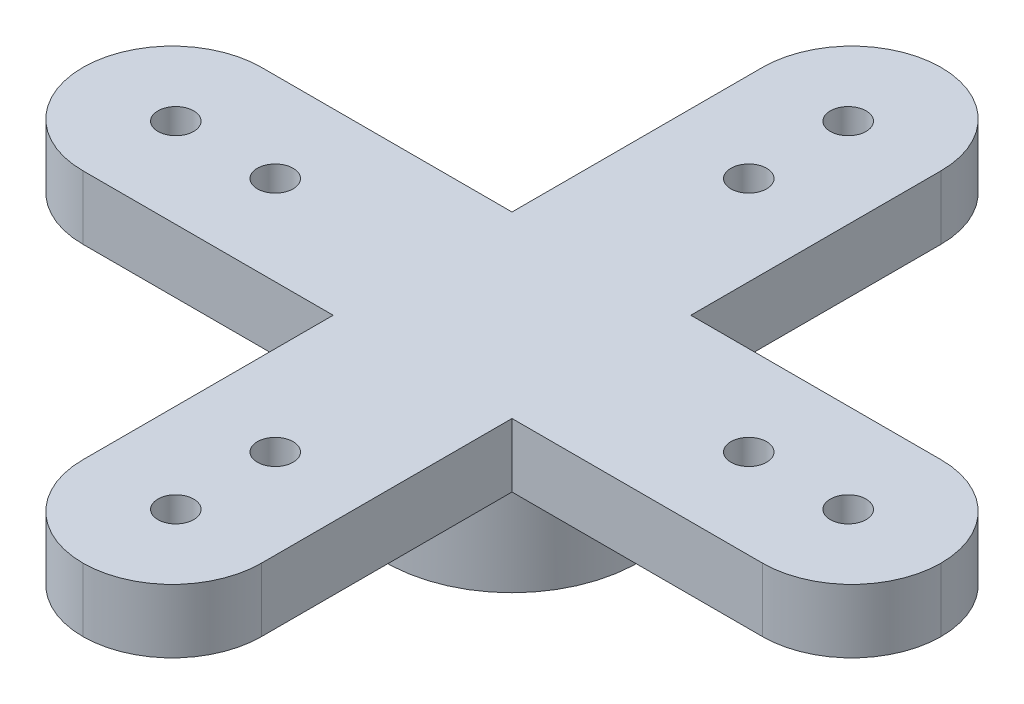
SolidWorks part; units mm, degrees
other "标注1"
sketch "草图3" plane through (0, 0, 14.5) normal (-0.6732, -0.6967, 0.2477) x (-0.1205, 0.4339, 0.8929)
ref_plane "前视基准面" through (0, 0, 0) normal (0, 0, 1) x (1, 0, 0)
ref_plane "上视基准面" through (0, 0, 0) normal (0, 1, 0) x (1, 0, 0)
ref_plane "右视基准面" through (0, 0, 0) normal (1, 0, 0) x (0, 0, -1)
sketch "草图1" plane through (0, 0, 0) normal (0, 1, 0) x (1, 0, 0)
  line L0 (0, 0) -> (9.5, 0)
  line L1 (24, 0) -> (24, -5)
  line L2 (24, -5) -> (14.5, -5)
  line L3 (0, -5) -> (0, 0)
  line L4 (24, -2.5) -> (12, -2.5) construction
  line L5 (12, 0) -> (12, -2.5) construction
  line L6 (14.5, 0) -> (24, 0)
  line L7 (14.5, 0) -> (14.5, 9.5)
  line L8 (14.5, 9.5) -> (9.5, 9.5)
  line L9 (9.5, 9.5) -> (9.5, 0)
  line L10 (9.5, -14.5) -> (14.5, -14.5)
  line L11 (14.5, -14.5) -> (14.5, -5)
  line L12 (9.5, -5) -> (9.5, -14.5)
  line L13 (9.5, -5) -> (0, -5)
extrude "凸台-拉伸1" add sketch "草图1" along normal blind 1.78
fillet "圆角1" radius 2.5 8 edges at (0, 0.89, 5) (0, 0.89, 0) (9.5, 0.89, -9.5) (14.5, 0.89, -9.5) (24, 0.89, 0) (24, 0.89, 5) (9.5, 0.89, 14.5) (14.5, 0.89, 14.5)
sketch "草图2" plane through (0, 1.78, 0) normal (0, 1, 0) x (1, 0, 0)
  line L1 (3.1, -2.5) -> (4.88, -2.5) construction
  line L2 (4.88, -2.5) -> (5.38, -2.5) construction
  line L3 (9.5, -5) -> (14.5, 0) construction
  line L4 (9.5, 0) -> (12, -2.5) construction
  line L5 (12, 6.4) -> (12, 4.62) construction
  line L6 (12, 4.62) -> (12, 4.12) construction
  line L7 (20.9, -2.5) -> (19.12, -2.5) construction
  line L24 (19.12, -2.5) -> (18.62, -2.5) construction
  line L25 (12, -11.4) -> (12, -9.62) construction
  line L26 (12, -9.62) -> (12, -9.12) construction
  circle A1 centre (2.6, -2.5) radius 0.5
  circle A2 centre (5.38, -2.5) radius 0.5
  circle A3 centre (12, 6.9) radius 0.5
  circle A4 centre (12, 4.12) radius 0.5
  circle A5 centre (21.4, -2.5) radius 0.5
  circle A6 centre (18.62, -2.5) radius 0.5
  circle A7 centre (12, -11.9) radius 0.5
  circle A24 centre (12, -9.12) radius 0.5
  dimension "D2" = 4
extrude "切除-拉伸2" cut sketch "草图2" against normal blind 1.78
sketch "草图4" plane through (0, 0, 0) normal (0, -1, 0) x (1, 0, 0)
  line L0 (9.5, 0) -> (14.5, 5) construction
  line L1 (9.5, 5) -> (14.5, 0) construction
  circle A0 centre (12, 2.5) radius 2
  circle A1 centre (12, 2.5) radius 3.5355
extrude "凸台-拉伸2" add sketch "草图4" along normal blind 2.44
